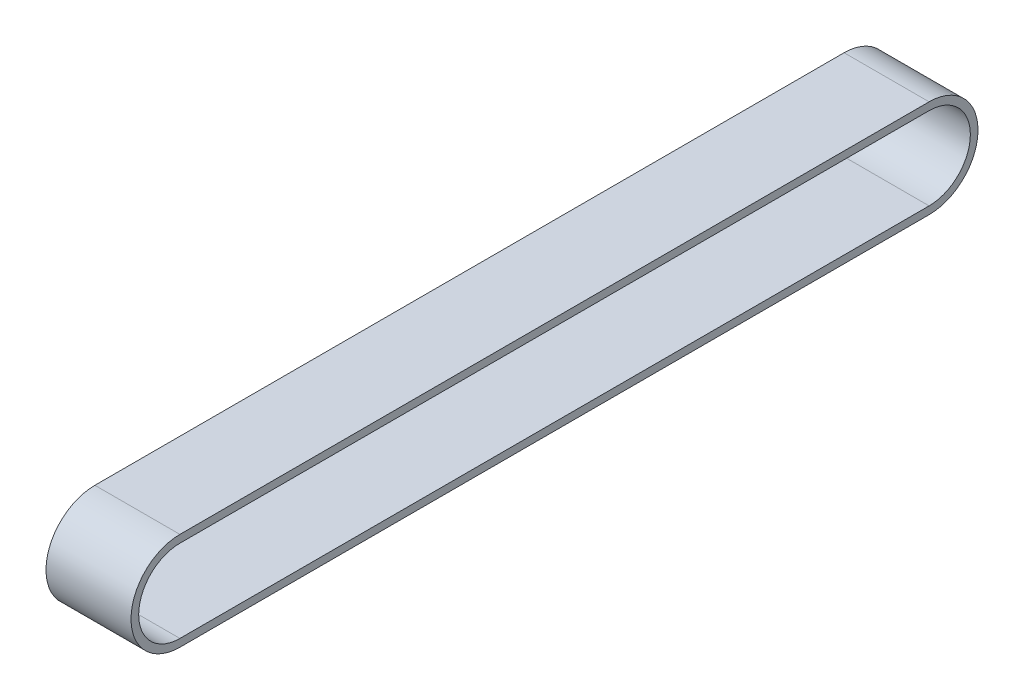
SolidWorks part; units mm, degrees
material "PUR"
ref_plane "Front" through (0, 0, 0) normal (0, 0, 1) x (1, 0, 0)
ref_plane "Top" through (0, 0, 0) normal (0, 1, 0) x (1, 0, 0)
ref_plane "Right" through (0, 0, 0) normal (1, 0, 0) x (0, 0, -1)
sketch "Sketch1" plane through (0, 0, 0) normal (1, 0, 0) x (0, 0, -1)
  line L0 (-111.9188, 0) -> (111.9188, 0) construction
  line L1 (-111.9188, 14.605) -> (111.9188, 14.605)
  line L2 (-111.9188, -14.605) -> (111.9188, -14.605)
  line L3 (-111.9188, 0) -> (111.9188, 0) construction
  line L4 (-111.9187, 12.319) -> (111.9187, 12.319)
  line L5 (-111.9187, -12.319) -> (111.9187, -12.319)
  arc A0 (-111.9188, 14.605) -> (-111.9188, -14.605) centre (-111.9188, 0) ccw
  arc A1 (111.9188, -14.605) -> (111.9188, 14.605) centre (111.9188, 0) ccw
  arc A2 (-111.9187, 12.319) -> (-111.9187, -12.319) centre (-111.9188, 0) ccw
  arc A3 (111.9187, -12.319) -> (111.9187, 12.319) centre (111.9188, 0) ccw
  point P2 (0, 0)
  point P9 (0, 0)
  dimension "D2" = 24.638
  dimension "D1" = 2.286
  dimension "D3" = 223.8375
extrude "Boss-Extrude1" add sketch "Sketch1" along normal mid plane 25.4
